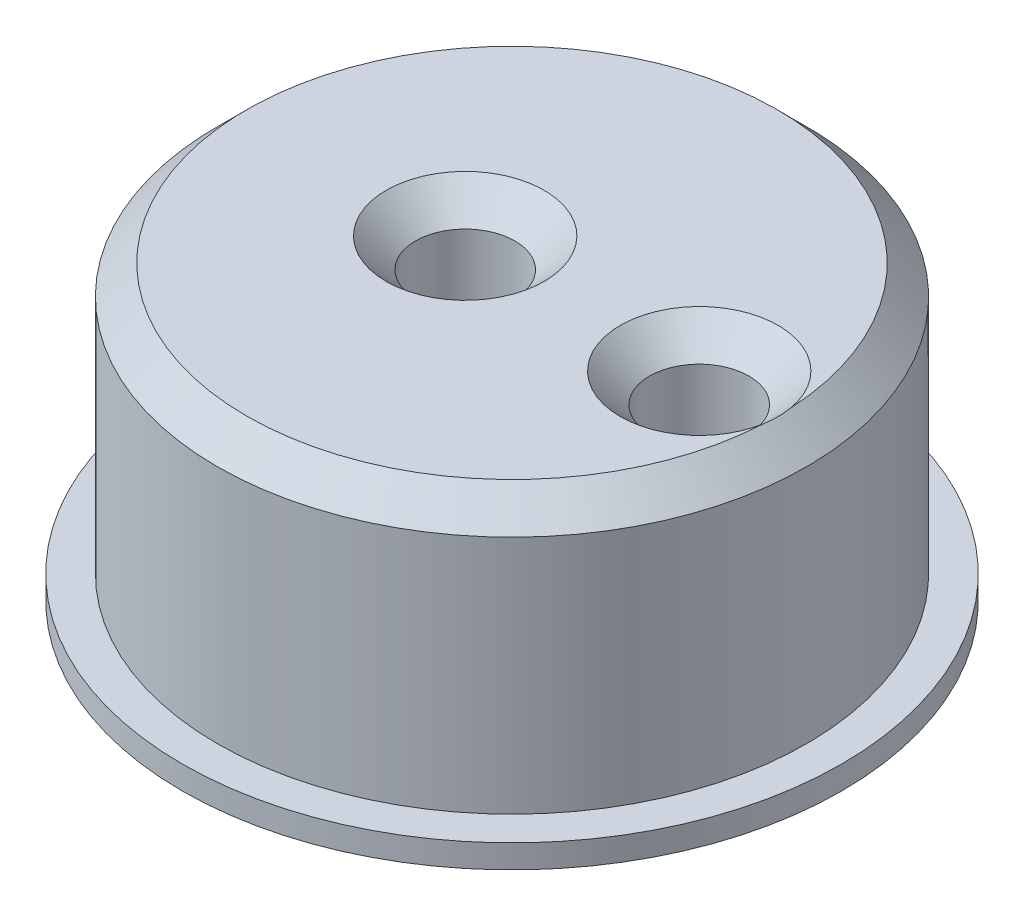
SolidWorks part; units mm, degrees
ref_plane "前视基准面" through (0, 0, 0) normal (0, 0, 1) x (1, 0, 0)
ref_plane "上视基准面" through (0, 0, 0) normal (0, 1, 0) x (1, 0, 0)
ref_plane "右视基准面" through (0, 0, 0) normal (1, 0, 0) x (0, 0, -1)
other "Configuration Table"
sketch "草图1" plane through (0, 0, 0) normal (0, 1, 0) x (1, 0, 0)
  line L0 (1.2, 6.4178) -> (1.2, -6.4114) construction
  line L1 (-5.7349, 0) -> (5.8104, 0) construction
  circle A0 centre (0, 0) radius 5.035
  circle A1 centre (3.2, 0) radius 0.85
  circle A2 centre (-0.8, 0) radius 0.85
  dimension "D1" = 10.07
  dimension "D3" = 4
  dimension "D4" = 1.7
  dimension "D2" = 1.2
extrude "凸台-拉伸1" add sketch "草图1" along normal blind 4.6
sketch "草图3" plane through (0, 0, 0) normal (0, -1, 0) x (1, 0, 0)
  circle A0 centre (3.2, 0) radius 0.85 construction
  circle A1 centre (0, 0) radius 5.035 construction
  circle A3 centre (-0.8, 0) radius 0.85 construction
  circle A4 centre (3.2, 0) radius 0.85
  circle A5 centre (-0.8, 0) radius 0.85
  circle A6 centre (0, 0) radius 5.035 construction
  circle A7 centre (0, 0) radius 5.635
  dimension "D1" = 0.6
extrude "凸台-拉伸2" add sketch "草图3" along normal blind 0.4
chamfer "倒角1" distance 0.5 angle 45 5 edges at (0, 4.6, 5.035) (-0.8, 4.6, -0.85) (3.2, 4.6, 0.85) (-0.8, -0.4, -0.85) (3.2, -0.4, -0.85)
ref_axis "基准轴1" through (0, 4.1, 0) along (0, -1, 0)
sketch "草图2" plane through (0, 0, 0) normal (0, 1, 0) x (1, 0, 0)
  line L0 (-5.9042, 0) -> (6.2358, 0) construction
